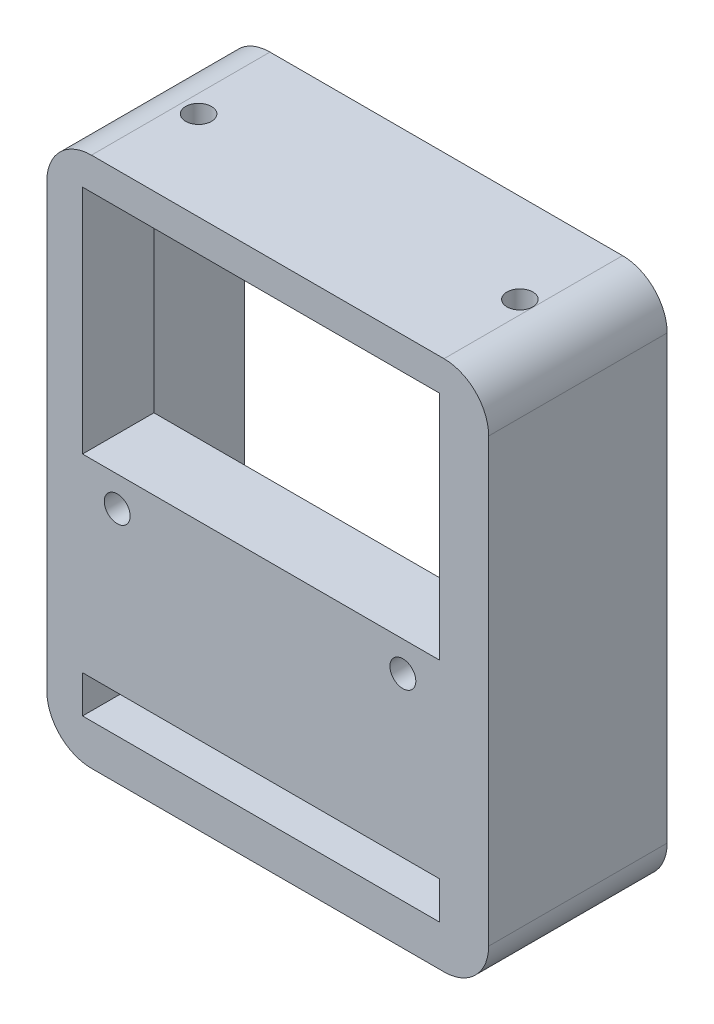
SolidWorks part; units mm, degrees
ref_plane "前视基准面" through (0, 0, 0) normal (0, 0, 1) x (1, 0, 0)
ref_plane "上视基准面" through (0, 0, 0) normal (0, 1, 0) x (1, 0, 0)
ref_plane "右视基准面" through (0, 0, 0) normal (1, 0, 0) x (0, 0, -1)
sketch "草图1" plane through (0, 0, 0) normal (0, 0, 1) x (1, 0, 0)
  line L1 (-19.75, 29.75) -> (19.75, 29.75)
  line L2 (-24.75, 24.75) -> (-24.75, -24.75)
  line L3 (-19.75, -29.75) -> (19.75, -29.75)
  line L4 (24.75, 24.75) -> (24.75, -24.75)
  line L5 (0, -29.75) -> (0, 29.75) construction
  line L6 (-24.75, 0) -> (24.75, 0) construction
  arc A0 (19.75, -29.75) -> (24.75, -24.75) centre (19.75, -24.75) ccw
  arc A1 (-24.75, -24.75) -> (-19.75, -29.75) centre (-19.75, -24.75) ccw
  arc A2 (19.75, 29.75) -> (24.75, 24.75) centre (19.75, 24.75) cw
  arc A3 (-19.75, 29.75) -> (-24.75, 24.75) centre (-19.75, 24.75) ccw
  point P0 (0, 0)
  point P8 (-24.75, -29.75)
  point P11 (24.75, 29.75)
  point P15 (-24.75, 29.75)
  dimension "D3" = 5
  dimension "D1" = 49.5
  dimension "D2" = 59.5
extrude "凸台-拉伸1" add sketch "草图1" along normal blind 20
sketch "草图2" plane through (0, 0, 0) normal (0, 0, -1) x (-1, 0, 0)
  line L1 (-22.6, 27.6) -> (22.6, 27.6)
  line L2 (-22.6, 27.6) -> (-22.6, -27.6)
  line L3 (-22.6, -27.6) -> (22.6, -27.6)
  line L4 (22.6, 27.6) -> (22.6, -27.6)
  line L5 (0, -27.6) -> (0, 27.6) construction
  line L6 (-22.6, 0) -> (22.6, 0) construction
  point P0 (0, 0)
  dimension "D1" = 45.2
  dimension "D2" = 55.2
extrude "切除-拉伸1" cut sketch "草图2" against normal blind 12
sketch "草图4" plane through (0, 0, 20) normal (0, 0, 1) x (1, 0, 0)
  line L0 (-19.75, -29.75) -> (19.75, -29.75) construction
  line L5 (-20.75, 26.15) -> (19.25, 26.15)
  line L6 (-20.75, 26.15) -> (-20.75, 0.25)
  line L7 (-20.75, 0.25) -> (19.25, 0.25)
  line L8 (19.25, 26.15) -> (19.25, 0.25)
  line L9 (-20.75, -20.965) -> (19.25, -20.965)
  line L10 (-20.75, -20.965) -> (-20.75, -25.165)
  line L11 (-20.75, -25.165) -> (19.25, -25.165)
  line L12 (19.25, -20.965) -> (19.25, -25.165)
  line L20 (19.75, 29.75) -> (-19.75, 29.75) construction
  line L21 (-24.75, 24.75) -> (-24.75, -24.75) construction
  dimension "D1" = 3.6
  dimension "D2" = 4
  dimension "D3" = 4.585
  dimension "D4" = 4.2
  dimension "D5" = 40
  dimension "D6" = 21.215
extrude "切除-拉伸2" cut sketch "草图4" against normal through all contours L8 L5 L6 L7 | L12 L9 L10 L11 region at (-0.75, 13.2, 20) region at (-0.75, -23.065, 20)
sketch "草图6" plane through (0, 0, 12) normal (0, 0, -1) x (-1, 0, 0)
  line L0 (-19.75, 29.75) -> (19.75, 29.75) construction
  line L2 (-24.75, -24.75) -> (-24.75, 24.75) construction
  circle A0 centre (16.862, -3.116) radius 1.45
  circle A1 centre (-15.138, -3.116) radius 1.45
  dimension "D4" = 2.9
  dimension "D1" = 32
  dimension "D2" = 32.866
  dimension "D3" = 9.612
extrude "切除-拉伸4" cut sketch "草图6" against normal through all
sketch "草图7" plane through (0, 0, 20) normal (0, 0, 1) x (1, 0, 0)
  circle A0 centre (-16.862, -3.116) radius 2.05
  circle A1 centre (15.138, -3.116) radius 2.05
  dimension "D1" = 4.1
extrude "切除-拉伸5" [suppressed] cut sketch "草图7" against normal blind 6
sketch "草图10" plane through (0, 0, 12) normal (0, 0, -1) x (-1, 0, 0)
  line L0 (-22.6, -27.6) -> (22.6, -27.6) construction
  line L5 (22.6, -27.6) -> (22.6, 27.6) construction
  line L6 (22.6, 27.6) -> (-22.6, 27.6) construction
  line L7 (-22.6, 27.6) -> (-22.6, -27.6) construction
  line L8 (-22.6, -27.6) -> (22.6, -27.6)
  line L9 (22.6, -27.6) -> (22.6, 27.6)
  line L10 (22.6, 27.6) -> (-22.6, 27.6)
  line L11 (-22.6, 27.6) -> (-22.6, -27.6)
  line L12 (-21.6, 26.6) -> (-21.6, -26.6)
  line L13 (-21.6, -26.6) -> (21.6, -26.6)
  line L14 (21.6, -26.6) -> (21.6, 26.6)
  line L15 (21.6, 26.6) -> (-21.6, 26.6)
  dimension "D1" = 1
extrude "凸台-拉伸2" [suppressed] add sketch "草图10" along normal blind 3.5
sketch "草图8" plane through (0, 29.75, 0) normal (0, 1, 0) x (1, 0, 0)
  line L0 (-24.75, -20) -> (-24.75, 0) construction
  line L1 (19.75, 0) -> (-19.75, 0) construction
  circle A0 centre (-17.75, -10) radius 1.45
  circle A1 centre (18.25, -10) radius 1.45
  dimension "D4" = 2.9
  dimension "D1" = 36
  dimension "D2" = 7
  dimension "D3" = 10
extrude "切除-拉伸6" cut sketch "草图8" against normal blind 6
sketch "草图9" plane through (0, -29.75, 0) normal (0, -1, 0) x (1, 0, 0)
  line L0 (0, 20) -> (0, 0) construction
  line L1 (-19.75, 20) -> (19.75, 20) construction
  circle A0 centre (-10, 10) radius 1.45
  circle A1 centre (10, 10) radius 1.45
  dimension "D3" = 2.9
  dimension "D1" = 10
  dimension "D2" = 10
extrude "切除-拉伸7" cut sketch "草图9" against normal blind 6
